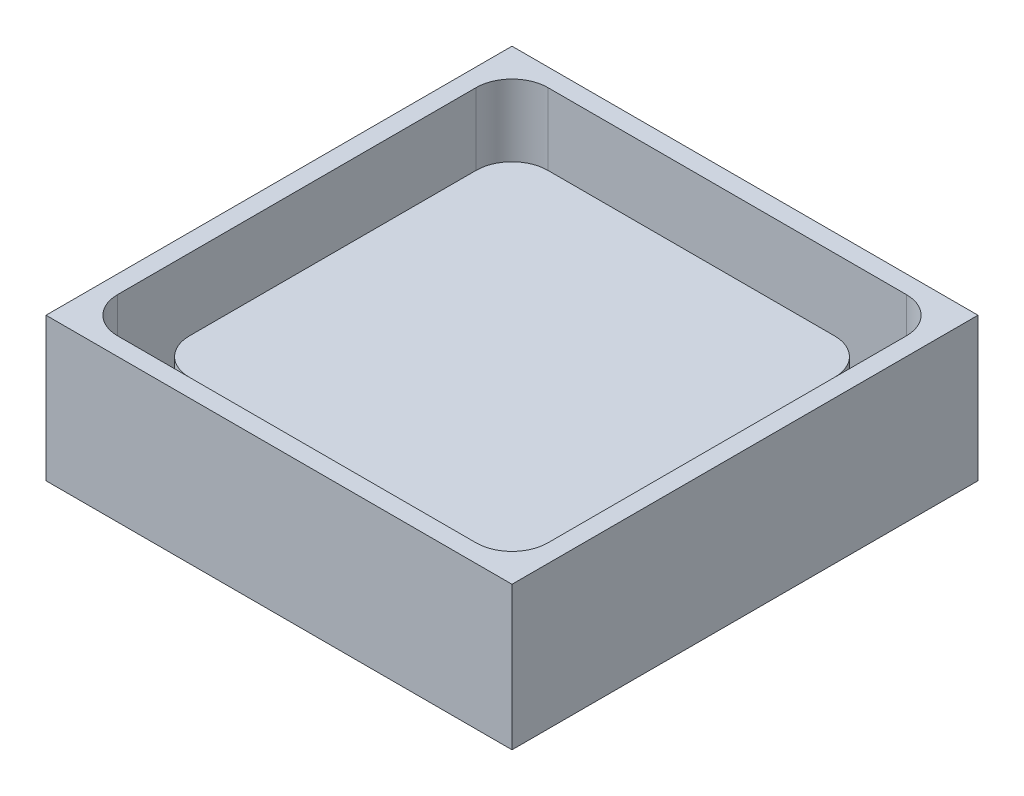
SolidWorks part; units mm, degrees
ref_plane "Front Plane" through (0, 0, 0) normal (0, 0, 1) x (1, 0, 0)
ref_plane "Top Plane" through (0, 0, 0) normal (0, 1, 0) x (1, 0, 0)
ref_plane "Right Plane" through (0, 0, 0) normal (1, 0, 0) x (0, 0, -1)
sketch "Sketch1" plane through (0, 0, 0) normal (0, 1, 0) x (1, 0, 0)
  line L1 (-10, -10) -> (10, -10)
  line L2 (-10, -10) -> (-10, 10)
  line L3 (-10, 10) -> (10, 10)
  line L4 (10, -10) -> (10, 10)
  line L5 (-10, -10) -> (10, 10) construction
  line L6 (-10, 10) -> (10, -10) construction
  point P0 (0, 0)
  dimension "D1" = 20
  dimension "D2" = 20
extrude "Boss-Extrude1" add sketch "Sketch1" along normal blind 6
sketch "Sketch2" plane through (0, 0, 0) normal (0, 1, 0) x (1, 0, 0)
  line L1 (-12, -12) -> (12, -12)
  line L2 (-12, -12) -> (-12, 12)
  line L3 (-12, 12) -> (12, 12)
  line L4 (12, -12) -> (12, 12)
  line L5 (-12, -12) -> (12, 12) construction
  line L6 (-12, 12) -> (12, -12) construction
  line L7 (-13, -13) -> (13, -13)
  line L8 (-13, -13) -> (-13, 13)
  line L9 (-13, 13) -> (13, 13)
  line L10 (13, -13) -> (13, 13)
  line L11 (-13, -13) -> (13, 13) construction
  line L12 (-13, 13) -> (13, -13) construction
  point P0 (0, 0)
  point P6 (0, 0)
  dimension "D1" = 24
  dimension "D2" = 24
  dimension "D3" = 26
  dimension "D4" = 26
extrude "Boss-Extrude2" add sketch "Sketch2" along normal blind 1 contours L2 L1 L4 L3
extrude "Boss-Extrude3" add sketch "Sketch2<3>" along normal blind 8
sketch "Sketch2<3>" plane through (0, 0, 0) normal (0, 1, 0) x (1, 0, 0) same geometry as "Sketch2"
fillet "Fillet1" radius 2 4 edges at (-10, 3.5, 10) (10, 3.5, 10) (10, 3.5, -10) (-10, 3.5, -10)
fillet "Fillet2" radius 2 4 edges at (12, 4.5, 12) (-12, 4.5, 12) (12, 4.5, -12) (-12, 4.5, -12)
